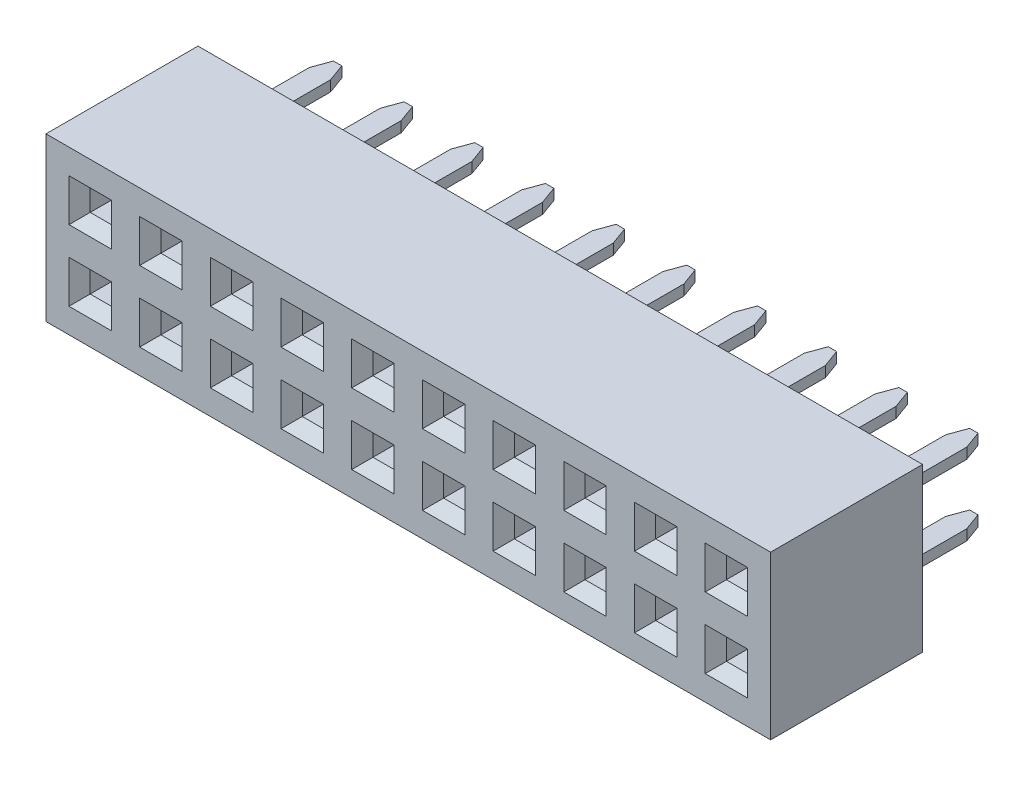
SolidWorks part; units mm, degrees
ref_plane "Спереди" through (0, 0, 0) normal (0, 0, 1) x (1, 0, 0)
ref_plane "Сверху" through (0, 0, 0) normal (0, 1, 0) x (1, 0, 0)
ref_plane "Справа" through (0, 0, 0) normal (1, 0, 0) x (0, 0, -1)
sketch "Эскиз1" plane through (0, 0, 0) normal (0, 0, 1) x (1, 0, 0)
  line L1 (-10.25, -2.3) -> (10.25, -2.3)
  line L2 (-10.25, -2.3) -> (-10.25, 2.3)
  line L3 (-10.25, 2.3) -> (10.25, 2.3)
  line L4 (10.25, -2.3) -> (10.25, 2.3)
  line L5 (-10.25, -2.3) -> (10.25, 2.3) construction
  line L6 (-10.25, 2.3) -> (10.25, -2.3) construction
  point P0 (0, 0)
  dimension "D1" = 20.5
  dimension "D2" = 4.6
extrude "Бобышка-Вытянуть1" add sketch "Эскиз1" along normal blind 4.3
sketch "Эскиз2" plane through (0, 0, 4.3) normal (0, 0, 1) x (1, 0, 0)
  line L1 (8.4, 1.6) -> (9.6, 1.6)
  line L2 (8.4, 1.6) -> (8.4, 0.4)
  line L3 (8.4, 0.4) -> (9.6, 0.4)
  line L4 (9.6, 1.6) -> (9.6, 0.4)
  line L5 (8.4, 1.6) -> (9.6, 0.4) construction
  line L6 (8.4, 0.4) -> (9.6, 1.6) construction
  line L7 (10.25, 2.3) -> (-10.25, 2.3) construction
  line L8 (10.25, -2.3) -> (10.25, 2.3) construction
  point P0 (9, 1)
  point P9 (0, 0)
  dimension "D1" = 1.25
  dimension "D2" = 1.3
  dimension "D3" = 1.2
extrude "Вырез-Вытянуть1" cut sketch "Эскиз2" against normal blind 0.3
chamfer "Фаска1" distance 0.3 angle 45 4 edges at (9, 0.4, 4) (9.6, 1, 4) (9, 1.6, 4) (8.4, 1, 4)
sketch "Эскиз3" plane through (0, 0, 4) normal (0, 0, 1) x (1, 0, 0)
  line L1 (8.7, 1.3) -> (9.3, 1.3)
  line L2 (8.7, 1.3) -> (8.7, 0.7)
  line L3 (8.7, 0.7) -> (9.3, 0.7)
  line L4 (9.3, 1.3) -> (9.3, 0.7)
extrude "Вырез-Вытянуть2" cut sketch "Эскиз3" against normal blind 2.25
sketch "Эскиз4" plane through (0, 0, 0) normal (0, 0, -1) x (-1, 0, 0)
  line L1 (-9.3, 0.85) -> (-8.7, 0.85)
  line L2 (-9.3, 0.85) -> (-9.3, 1.15)
  line L3 (-9.3, 1.15) -> (-8.7, 1.15)
  line L4 (-8.7, 0.85) -> (-8.7, 1.15)
  line L5 (-9.3, 0.85) -> (-8.7, 1.15) construction
  line L6 (-9.3, 1.15) -> (-8.7, 0.85) construction
  point P0 (-9, 1)
  dimension "D1" = 0.6
  dimension "D2" = 0.3
extrude "Бобышка-Вытянуть2" add sketch "Эскиз4" along normal blind 2.7
chamfer "Фаска2" distance 0.5 angle 20 2 edges at (8.7, 1, -2.7) (9.3, 1, -2.7) first distance on face at (8.7, 1, -1.35) first distance on face at (9.3, 1, -1.35)
pattern_linear "Линейный массив1" count 10 spacing 2 along (-1, 0, 0) count 2 spacing 2 along (0, -1, 0) of "Вырез-Вытянуть1", "Фаска1", "Вырез-Вытянуть2"
pattern_linear "Линейный массив2" count 10 spacing 2 along (-1, 0, 0) count 2 spacing 2 along (0, -1, 0) of "Бобышка-Вытянуть2", "Фаска2"
equation "\"N\"= 10"
equation "\"D1@Эскиз1\"=2*\"N\"+0.5"
equation "\"D1@Линейный массив1\"=\"N\""
equation "\"D1@Линейный массив2\"=\"N\""
